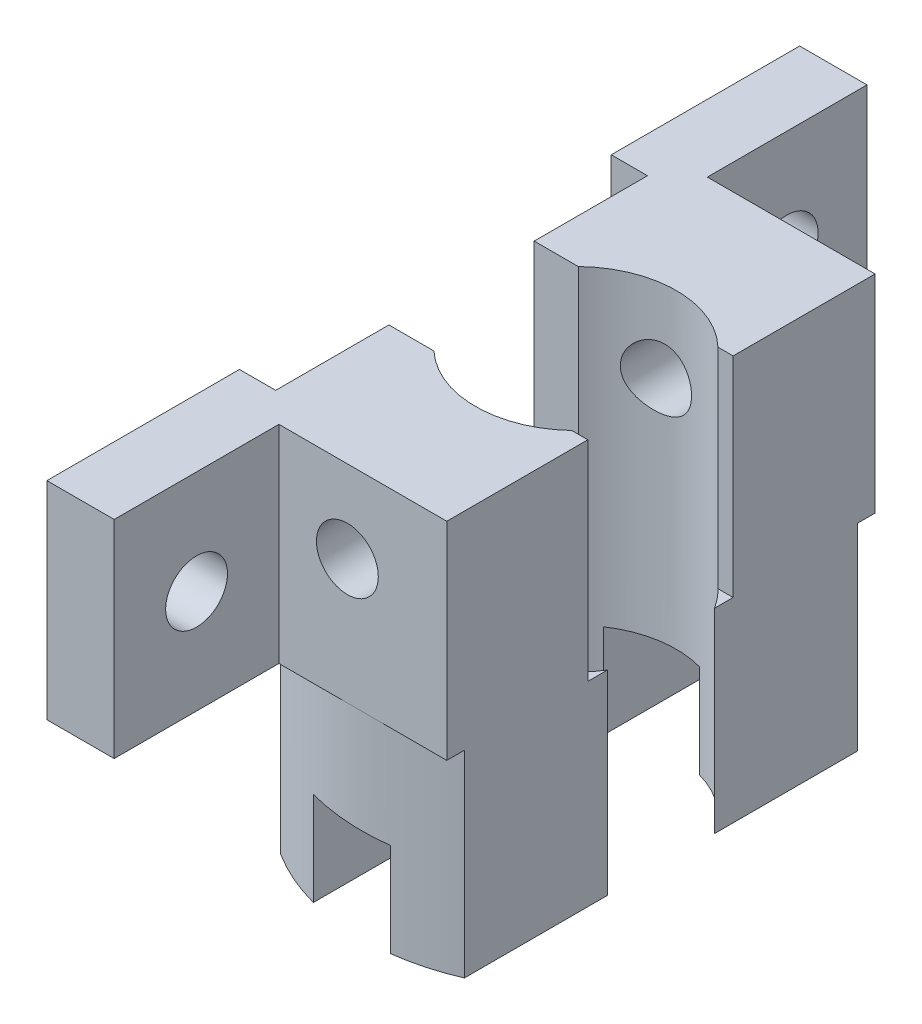
SolidWorks part; units mm, degrees
ref_plane "前基準面" through (0, 0, 0) normal (0, 0, 1) x (1, 0, 0)
ref_plane "上基準面" through (0, 0, 0) normal (0, 1, 0) x (1, 0, 0)
ref_plane "右基準面" through (0, 0, 0) normal (1, 0, 0) x (0, 0, -1)
sketch "草圖1" plane through (0, 0, 0) normal (0, 1, 0) x (1, 0, 0)
  circle A0 centre (0, 0) radius 9.68
  dimension "D1" = 19.36
extrude "伸長-薄件1" add sketch "草圖1" along normal blind 116.68 thin thin type one direction wall 11
ref_plane "平面1" through (-21, 0, 0) normal (1, 0, 0) x (0, 0, -1)
sketch "草圖11" plane through (0, 116.68, 0) normal (0, 1, 0) x (1, 0, 0)
  line L0 (-993.1634, -44.2358) -> (49006.8366, -44.2358) construction
  line L2 (35.2085, 30.7642) -> (8.2085, 30.7642)
  line L3 (35.2085, 30.7642) -> (35.2085, -119.2358)
  line L4 (35.2085, -119.2358) -> (8.2085, -119.2358)
  line L5 (8.2085, 30.7642) -> (8.2085, -119.2358)
  line L6 (35.2085, 30.7642) -> (8.2085, -119.2358) construction
  line L7 (35.2085, -119.2358) -> (8.2085, 30.7642) construction
  circle A0 centre (0, 0) radius 20.68 construction
  point P1 (21.7085, -44.2358)
  dimension "D1" = 150
  dimension "D2" = 27
  dimension "D3" = 30.7642
extrude "除料-伸長3" cut sketch "草圖11" against normal blind 40
ref_plane "平面2" through (0, 0, 21) normal (0, 0, 1) x (1, 0, 0)
sketch "草圖13" plane through (0, 0, 21) normal (0, 0, 1) x (1, 0, 0)
  line L0 (-21, -22.649) -> (-21, 22.649) construction
  line L1 (-21, 122.7847) -> (-11, 122.7847)
  line L2 (-21, 122.7847) -> (-21, -5.5603)
  line L3 (-21, -5.5603) -> (-11, -5.5603)
  line L4 (-11, 122.7847) -> (-11, -5.5603)
  dimension "D1" = 10
extrude "除料-伸長7" cut sketch "草圖13" against normal through all
sketch "草圖15" plane through (0, 0, 21) normal (0, 0, 1) x (1, 0, 0)
  line L0 (-1.3957, -883.32) -> (-1.3957, 49116.68) construction
  line L1 (8.2085, 116.68) -> (-11, 116.68) construction
  line L2 (-11, 0) -> (20.68, 0) construction
  line L3 (2.6043, 86.68) -> (-5.3957, 86.68)
  line L4 (2.6043, 86.68) -> (2.6043, 18)
  line L5 (2.6043, 18) -> (-5.3957, 18)
  line L6 (-5.3957, 86.68) -> (-5.3957, 18)
  line L7 (2.6043, 86.68) -> (-5.3957, 18) construction
  line L8 (2.6043, 18) -> (-5.3957, 86.68) construction
  point P1 (-1.3957, 52.34)
  point P5 (-1.3957, 116.68)
  dimension "D1" = 30
  dimension "D2" = 18
  dimension "D3" = 8
extrude "除料-伸長9" cut sketch "草圖15" against normal blind 48
sketch "草圖16" plane through (8.2085, 0, 0) normal (1, 0, 0) x (0, 0, -1)
  line L0 (20.68, 86.68) -> (20.68, 116.68) construction
  line L1 (5.1306, 116.68) -> (20.68, 116.68)
  line L2 (5.1306, 116.68) -> (5.1306, 96.68)
  line L3 (5.1306, 96.68) -> (20.68, 96.68)
  line L4 (20.68, 116.68) -> (20.68, 96.68)
  line L5 (-5.1306, 76.68) -> (-5.1306, 116.68) construction
  line L6 (-5.1306, 96.68) -> (-20.59, 96.68)
  line L7 (-5.1306, 96.68) -> (-5.1306, 116.68)
  line L8 (-5.1306, 116.68) -> (-20.59, 116.68)
  line L9 (-20.59, 96.68) -> (-20.59, 116.68)
  line L10 (-17.5118, 116.68) -> (-20.68, 116.68) construction
  dimension "D1" = 20
extrude "填料-伸長4" add sketch "草圖16" against normal blind 19.2
sketch "草圖17" plane through (0, 116.68, 0) normal (0, 1, 0) x (1, 0, 0)
  line L0 (-1009.59, 0) -> (48990.41, 0) construction
  line L1 (8.2085, 20.68) -> (8.2085, 5.1306) construction
  line L2 (8.2085, 6.97) -> (-11, 6.97)
  line L3 (8.2085, 6.97) -> (8.2085, -7.06)
  line L4 (8.2085, -7.06) -> (-11, -7.06)
  line L5 (-11, 6.97) -> (-11, -7.06)
  line L6 (-11, -17.5118) -> (-11, 17.5118) construction
  line L7 (-10.9915, -20.59) -> (-1.9273, -20.59) construction
  arc A0 (-8.2085, 5.1306) -> (-8.2085, -5.1306) centre (0, 0) ccw construction
  point P6 (-9.68, 0)
  dimension "D1" = 14.03
  dimension "D2" = 13.53
extrude "除料-伸長10" cut sketch "草圖17" against normal blind 20.2
sketch "草圖18" plane through (0, 0, 0) normal (0, -1, 0) x (1, 0, 0)
  circle A0 centre (0, 0) radius 9.59
extrude "除料-伸長11" cut sketch "草圖18" against normal through all
sketch "草圖21" plane through (0, 0, -20.68) normal (0, 0, -1) x (-1, 0, 0)
  line L0 (1.3915, 96.68) -> (1.3915, 105.73) construction
  line L1 (0, 96.68) -> (10.9915, 96.68) construction
  line L2 (1.3915, 105.73) -> (1.3915, 108.73) construction
  circle A0 centre (1.3915, 108.73) radius 2.985
  dimension "D3" = 5.97
  dimension "D1" = 9.05
  dimension "D2" = 3
extrude "除料-伸長12" cut sketch "草圖21" against normal blind 55.2
sketch "草圖23" plane through (0, 0, -20.68) normal (0, 0, -1) x (-1, 0, 0)
  line L0 (1.3915, 105.745) -> (1.3915, -11.785) construction
  circle A0 centre (1.3915, 108.73) radius 2.985 construction
  dimension "D1" = 117.53
sketch "草圖24" plane through (0, 0, 0) normal (0, -1, 0) x (1, 0, 0)
  circle A0 centre (0, 0) radius 9.59
extrude "伸長-薄件2" add sketch "草圖24" along normal blind 55.2 thin thin type one direction wall 11
sketch "草圖25" plane through (0, 0, 21) normal (0, 0, 1) x (1, 0, 0)
  line L0 (-1.3915, -11.785) -> (22.6124, -11.785)
  line L1 (22.6124, -11.785) -> (22.6124, -63.8733)
  line L2 (-22.7495, -63.8733) -> (22.6124, -63.8733)
  line L3 (-22.7495, -63.8733) -> (-22.7495, -11.785)
  line L4 (-22.7495, -11.785) -> (-1.3915, -11.785)
extrude "除料-伸長13" cut sketch "草圖25" against normal blind 55.2
sketch "草圖26" plane through (0, 0, 0) normal (0, 1, 0) x (1, 0, 0)
  line L0 (-21, -22.649) -> (-21, 22.649) construction
  line L1 (-10.9915, 20.68) -> (-21, 20.68)
  line L2 (-10.9915, 20.68) -> (-10.9915, -21)
  line L3 (-10.9915, -21) -> (-21, -21)
  line L4 (-21, 20.68) -> (-21, -21)
  line L5 (-17.6, -21) -> (17.6, -21) construction
extrude "除料-伸長15" cut sketch "草圖26" against normal blind 55.2
ref_plane "平面3" through (21, 0, 0) normal (1, 0, 0) x (0, 0, -1)
sketch "草圖27" plane through (21, 0, 0) normal (1, 0, 0) x (0, 0, -1)
  line L0 (0, -923.32) -> (0, 49076.68) construction
  line L1 (5.1306, 76.68) -> (-5.1306, 76.68) construction
  line L2 (18.9811, 76.68) -> (-18.9811, 76.68) construction
  line L3 (-5, 61.68) -> (5, 61.68)
  line L4 (-5, 61.68) -> (-5, 21.68)
  line L5 (-5, 21.68) -> (5, 21.68)
  line L6 (5, 61.68) -> (5, 21.68)
  line L7 (-5, 61.68) -> (5, 21.68) construction
  line L8 (-5, 21.68) -> (5, 61.68) construction
  point P1 (0, 41.68)
  point P5 (0, 76.68)
  dimension "D1" = 15
  dimension "D2" = 40
  dimension "D3" = 10
extrude "除料-伸長16" cut sketch "草圖27" against normal blind 55.2
sketch "草圖28" plane through (21, 0, 0) normal (1, 0, 0) x (0, 0, -1)
  line L1 (-22.4403, 4.804) -> (22.4403, 4.804)
  line L2 (-22.4403, 4.804) -> (-22.4403, -4.804)
  line L3 (-22.4403, -4.804) -> (22.4403, -4.804)
  line L4 (22.4403, 4.804) -> (22.4403, -4.804)
  line L5 (-22.4403, 4.804) -> (22.4403, -4.804) construction
  line L6 (-22.4403, -4.804) -> (22.4403, 4.804) construction
  point P0 (0, 0)
extrude "除料-伸長17" cut sketch "草圖28" against normal blind 12.2
sketch "草圖35" plane through (-10.9915, 0, 0) normal (-1, 0, 0) x (0, 0, 1)
  line L0 (20.59, 116.68) -> (20.59, 96.68)
  line L1 (20.59, 96.68) -> (7.06, 96.68)
  line L2 (7.06, 96.68) -> (7.06, 116.68)
  line L3 (7.06, 116.68) -> (20.59, 116.68)
extrude "填料-伸長10" add sketch "草圖35" along normal blind 15
sketch "草圖36" plane through (-10.9915, 0, 0) normal (-1, 0, 0) x (0, 0, 1)
  line L0 (-20.68, 116.68) -> (-6.97, 116.68)
  line L1 (-6.97, 116.68) -> (-6.97, 96.48)
  line L2 (-6.97, 96.48) -> (-20.68, 96.68)
  line L3 (-20.68, 96.68) -> (-20.68, 116.68)
extrude "填料-伸長11" add sketch "草圖36" along normal blind 15
sketch "草圖37" plane through (0, 0, 20.59) normal (0, 0, 1) x (1, 0, 0)
  line L0 (-25.9915, 96.68) -> (-1.9273, 96.68) construction
  line L1 (-25.9915, 116.68) -> (-16.9915, 116.68)
  line L2 (-25.9915, 116.68) -> (-25.9915, 96.68)
  line L3 (-25.9915, 96.68) -> (-16.9915, 96.68)
  line L4 (-16.9915, 116.68) -> (-16.9915, 96.68)
  dimension "D1" = 9
extrude "填料-伸長12" add sketch "草圖37" along normal blind 20
sketch "草圖38" plane through (0, 0, -20.68) normal (0, 0, -1) x (-1, 0, 0)
  line L0 (25.9915, 116.68) -> (-8.2085, 116.68) construction
  line L1 (25.9915, 96.68) -> (16.9915, 96.68)
  line L2 (25.9915, 96.68) -> (25.9915, 116.68)
  line L3 (25.9915, 116.68) -> (16.9915, 116.68)
  line L4 (16.9915, 96.68) -> (16.9915, 116.68)
  dimension "D1" = 9
extrude "填料-伸長13" add sketch "草圖38" along normal blind 20
sketch "草圖42" plane through (-16.9915, 0, 0) normal (1, 0, 0) x (0, 0, -1)
  line L0 (30.68, -903.32) -> (30.68, 49096.68) construction
  line L1 (40.68, 96.68) -> (20.68, 96.68) construction
  line L2 (-959.32, 106.68) -> (49040.68, 106.68) construction
  line L3 (40.68, 116.68) -> (40.68, 96.68) construction
  line L4 (-30.59, -903.32) -> (-30.59, 49096.68) construction
  line L5 (-40.59, 96.68) -> (-20.59, 96.68) construction
  circle A0 centre (30.68, 106.5544) radius 2.985
  circle A1 centre (-30.3956, 106.68) radius 2.985
  point P5 (30.68, 96.68)
  point P10 (40.68, 106.68)
  point P15 (-30.59, 96.68)
  dimension "D1" = 5.97
  dimension "D2" = 5.97
extrude "除料-伸長21" cut sketch "草圖42" against normal blind 20
sketch "草圖43" plane through (0, 116.68, 0) normal (0, 1, 0) x (1, 0, 0)
  line L0 (-11, 6.97) -> (-10.9915, 20.68)
  line L1 (-10.9915, 20.68) -> (-10.9915, 48.0968)
  line L2 (-10.9915, 48.0968) -> (-28.2748, 48.0968)
  line L3 (-28.2748, 48.0968) -> (-28.2748, -43.2705)
  line L4 (-28.2748, -43.2705) -> (-11, -43.2705)
  line L5 (-11, -43.2705) -> (-11, 6.97)
extrude "除料-伸長23" cut sketch "草圖43" against normal through all
sketch "草圖45" plane through (0, 0, 20.59) normal (0, 0, 1) x (1, 0, 0)
  line L0 (-11, 96.68) -> (-1.9273, 96.68) construction
  line L1 (-11, 116.68) -> (-8, 116.68)
  line L2 (-11, 116.68) -> (-11, 96.68)
  line L3 (-11, 96.68) -> (-8, 96.68)
  line L4 (-8, 116.68) -> (-8, 96.68)
  dimension "D1" = 3
extrude "填料-伸長14" add sketch "草圖45" along normal blind 30
sketch "草圖46" plane through (0, 0, -20.68) normal (0, 0, -1) x (-1, 0, 0)
  line L0 (0, 96.68) -> (10.9915, 96.68) construction
  line L1 (10.9915, 116.68) -> (7.9915, 116.68)
  line L2 (10.9915, 116.68) -> (10.9915, 96.68)
  line L3 (10.9915, 96.68) -> (7.9915, 96.68)
  line L4 (7.9915, 116.68) -> (7.9915, 96.68)
  dimension "D1" = 3
extrude "填料-伸長15" add sketch "草圖46" along normal blind 30
sketch "草圖47" plane through (-11, 0, 0) normal (-1, 0, 0) x (0, 0, 1)
  line L0 (50.59, 116.68) -> (7.06, 116.68) construction
  line L1 (50.59, 96.68) -> (17.5118, 96.68)
  line L2 (50.59, 96.68) -> (50.59, 116.68)
  line L3 (50.59, 116.68) -> (17.5118, 116.68)
  line L4 (17.5118, 96.68) -> (17.5118, 116.68)
extrude "填料-伸長16" add sketch "草圖47" along normal blind 50
sketch "草圖48" plane through (-10.9915, 0, 0) normal (-1, 0, 0) x (0, 0, 1)
  line L1 (-50.68, 116.68) -> (-20.68, 116.68)
  line L2 (-50.68, 116.68) -> (-50.68, 96.68)
  line L3 (-50.68, 96.68) -> (-20.68, 96.68)
  line L4 (-20.68, 116.68) -> (-20.68, 96.68)
extrude "填料-伸長17" add sketch "草圖48" along normal blind 50
sketch "草圖50" plane through (0, 0, 17.5118) normal (0, 0, -1) x (-1, 0, 0)
  line L0 (11, 96.68) -> (11, 116.68)
  line L1 (11, 116.68) -> (61, 116.68)
  line L2 (61, 116.68) -> (61, 96.68)
  line L3 (61, 96.68) -> (11, 96.68)
extrude "填料-伸長18" add sketch "草圖50" along normal blind 1
sketch "草圖51" plane through (0, 0, -20.68) normal (0, 0, 1) x (1, 0, 0)
  line L0 (-10.9915, 116.68) -> (-10.9915, 96.68)
  line L1 (-10.9915, 96.68) -> (-60.9915, 96.68)
  line L2 (-60.9915, 96.68) -> (-60.9915, 116.68)
  line L3 (-60.9915, 116.68) -> (-10.9915, 116.68)
extrude "填料-伸長19" add sketch "草圖51" along normal blind 1
sketch "草圖52" plane through (0, 116.68, 0) normal (0, 1, 0) x (1, 0, 0)
  line L0 (-34.4915, -949.32) -> (-34.4915, 49050.68) construction
  line L1 (-60.9915, 50.68) -> (-7.9915, 50.68) construction
  line L2 (-1007.9915, 35.68) -> (48992.0085, 35.68) construction
  line L3 (-7.9915, 50.68) -> (-7.9915, 20.68) construction
  line L4 (-60.9915, 19.68) -> (-60.9915, 50.68) construction
  line L5 (-7.9915, 50.68) -> (-60.9915, 50.68)
  line L6 (-7.9915, 50.68) -> (-7.9915, 36.68)
  line L7 (-7.9915, 36.68) -> (-60.9915, 36.68)
  line L8 (-60.9915, 50.68) -> (-60.9915, 36.68)
  point P5 (-34.4915, 50.68)
  point P10 (-7.9915, 35.68)
  dimension "D1" = 14
extrude "除料-伸長24" cut sketch "草圖52" against normal through all
sketch "草圖53" plane through (0, 116.68, 0) normal (0, 1, 0) x (1, 0, 0)
  line L0 (-61, -50.59) -> (-61, -16.5118) construction
  line L1 (-8, -50.59) -> (-61, -50.59)
  line L2 (-8, -50.59) -> (-8, -36.59)
  line L3 (-8, -36.59) -> (-61, -36.59)
  line L4 (-61, -50.59) -> (-61, -36.59)
  dimension "D1" = 14
extrude "除料-伸長25" cut sketch "草圖53" against normal through all
sketch "草圖54" plane through (0, 116.68, 0) normal (0, 1, 0) x (1, 0, 0)
  line L0 (-60.9915, 36.68) -> (-7.9915, 36.68) construction
  line L1 (-61, -36.59) -> (-21, -36.59)
  line L2 (-61, -36.59) -> (-61, 36.68)
  line L3 (-61, 36.68) -> (-21, 36.68)
  line L4 (-21, -36.59) -> (-21, 36.68)
  dimension "D1" = 40
extrude "除料-伸長26" cut sketch "草圖54" against normal through all
sketch "草圖55" plane through (0, 116.68, 0) normal (0, 1, 0) x (1, 0, 0)
  line L0 (-15.0276, -36.59) -> (-15.0276, -16.5118) construction
  line L1 (-8, -36.59) -> (-21, -36.59) construction
  line L2 (-21, -16.5118) -> (-11, -16.5118) construction
  line L3 (-13.4574, 19.68) -> (-13.4574, 39.76) construction
  line L4 (-10.9921, 19.68) -> (-21, 19.68) construction
  dimension "D1" = 20.08
sketch "草圖56" plane through (0, 0, -36.68) normal (0, 0, -1) x (-1, 0, 0)
  line L1 (7.9915, 96.68) -> (21, 96.68)
  line L2 (7.9915, 96.68) -> (7.9915, 116.68)
  line L3 (7.9915, 116.68) -> (21, 116.68)
  line L4 (21, 96.68) -> (21, 116.68)
extrude "填料-伸長21" add sketch "草圖56" along normal blind 3.08
ref_plane "平面4" through (0, 0, 50) normal (0, 0, 1) x (1, 0, 0)
sketch "草圖58" plane through (0, 0, 50) normal (0, 0, 1) x (1, 0, 0)
  line L1 (-22.571, -18.3082) -> (22.1011, -18.3082)
  line L2 (-22.571, -18.3082) -> (-22.571, 77.6317)
  line L3 (-22.571, 77.6317) -> (22.1011, 77.6317)
  line L4 (22.1011, -18.3082) -> (22.1011, 77.6317)
extrude "除料-伸長28" cut sketch "草圖58" against normal through all
sketch "草圖59" plane through (0, 77.6317, 0) normal (0, -1, 0) x (1, 0, 0)
  circle A0 centre (0, 0) radius 9.7
  dimension "D1" = 19.4
extrude "除料-伸長29" cut sketch "草圖59" against normal through all
sketch "草圖60" plane through (0, 116.68, 0) normal (0, 1, 0) x (1, 0, 0)
  line L0 (-21, 39.76) -> (-7.9915, 39.76) construction
  line L1 (-21, -36.59) -> (-14.4957, -36.59)
  line L2 (-21, -36.59) -> (-21, 39.76)
  line L3 (-21, 39.76) -> (-14.4957, 39.76)
  line L4 (-14.4957, -36.59) -> (-14.4957, 39.76)
extrude "除料-伸長30" cut sketch "草圖60" against normal through all
sketch "草圖61" plane through (0, 116.68, 0) normal (0, 1, 0) x (1, 0, 0)
  line L0 (1.9273, -20.59) -> (1.9273, -22.3991)
  line L1 (1.9273, -22.3991) -> (-2.1742, -21.4215)
  line L2 (-2.1742, -21.4215) -> (-2.1742, -20.59)
  line L3 (-8, -20.59) -> (-1.9273, -20.59) construction
  line L4 (-2.1742, -20.59) -> (1.9273, -20.59)
extrude "除料-伸長32" cut sketch "草圖61" against normal blind 20
sketch "草圖64" plane through (0, 116.68, 0) normal (0, 1, 0) x (1, 0, 0)
  line L1 (-8, -20.59) -> (8.2085, -20.59)
  line L2 (-8, -20.59) -> (-8, -20.68)
  line L3 (-8, -20.68) -> (8.2085, -20.68)
  line L4 (8.2085, -20.59) -> (8.2085, -20.68)
  dimension "D1" = 0.09
extrude "填料-伸長22" add sketch "草圖64" against normal blind 20
sketch "草圖65" plane through (0, 116.68, 0) normal (0, 1, 0) x (1, 0, 0)
  line L0 (-11, 6.97) -> (-10.9921, 19.68) construction
  line L1 (-11, -7.06) -> (-11, -16.5118) construction
  line L2 (-14.4957, -36.59) -> (-14.4957, -16.5118) construction
  line L3 (-11, -16.5118) -> (-14.4957, -16.5118)
  line L4 (-11, -16.5118) -> (-11, -19.7718)
  line L5 (-11, -19.7718) -> (-14.4957, -19.7718)
  line L6 (-14.4957, -16.5118) -> (-14.4957, -19.7718)
  dimension "D1" = 12.71
  dimension "D2" = 9.4518
  dimension "D3" = 3.26
extrude "除料-伸長33" cut sketch "草圖65" against normal through all
sketch "草圖66" plane through (0, 96.48, 0) normal (0, 1, 0) x (1, 0, 0)
  line L0 (-1011, -0.045) -> (48989, -0.045) construction
  line L1 (-11, 6.97) -> (-11, -7.06) construction
  line L2 (-12.9194, -0.045) -> (-12.9194, 17.905) construction
  line L3 (-12.9194, -0.045) -> (-12.9194, -17.995) construction
  line L4 (-11, -19.7718) -> (-11, -7.06) construction
  line L5 (-14.4957, -19.7718) -> (-11, -19.7718)
  line L6 (-14.4957, -19.7718) -> (-14.4957, -17.995)
  line L7 (-14.4957, -17.995) -> (-11, -17.995)
  line L8 (-11, -19.7718) -> (-11, -17.995)
  line L10 (-10.9921, 19.68) -> (-14.4957, 19.68)
  line L11 (-10.9921, 19.68) -> (-10.9921, 17.905)
  line L12 (-10.9921, 17.905) -> (-14.4957, 17.905)
  line L13 (-14.4957, 19.68) -> (-14.4957, 17.905)
  point P5 (-11, -0.045)
  dimension "D1" = 17.95
  dimension "D2" = 17.95
extrude "填料-伸長23" add sketch "草圖66" along normal blind 20.2
sketch "草圖68" plane through (0, 116.68, 0) normal (0, 1, 0) x (1, 0, 0)
  line L0 (-10.9932, 17.905) -> (-10.9932, 39.76) construction
  line L1 (-14.4957, 39.76) -> (-7.9915, 39.76) construction
  line L2 (-14.4957, 17.905) -> (-14.4957, 39.76) construction
  line L3 (-7.9915, 39.76) -> (-14.4957, 39.76)
  line L4 (-7.9915, 39.76) -> (-7.9915, 36.1)
  line L5 (-7.9915, 36.1) -> (-14.4957, 36.1)
  line L6 (-14.4957, 39.76) -> (-14.4957, 36.1)
  dimension "D1" = 3.66
extrude "除料-伸長34" cut sketch "草圖68" against normal blind 20
sketch "草圖69" plane through (-7.9915, 0, 0) normal (1, 0, 0) x (0, 0, -1)
  line L0 (28.39, -903.32) -> (28.39, 49096.68) construction
  line L1 (36.1, 96.68) -> (20.68, 96.68) construction
  line L2 (-28.635, -903.32) -> (-28.635, 49096.68) construction
  line L3 (-36.59, 96.68) -> (-20.68, 96.68) construction
  line L4 (-963.9, 106.68) -> (49036.1, 106.68) construction
  line L5 (36.1, 96.68) -> (36.1, 116.68) construction
  circle A0 centre (28.39, 106.68) radius 2.985
  circle A1 centre (-28.635, 106.68) radius 2.985
  point P5 (28.39, 96.68)
  point P10 (-28.635, 96.68)
  point P15 (36.1, 106.68)
  dimension "D1" = 5.97
  dimension "D2" = 5.97
extrude "除料-伸長35" cut sketch "草圖69" against normal through all
sketch "草圖70" plane through (0, 0, 20.59) normal (0, 0, -1) x (-1, 0, 0)
  circle A0 centre (1.3915, 108.73) radius 2.985
  dimension "D1" = 5.97
extrude "除料-伸長36" cut sketch "草圖70" against normal through all
